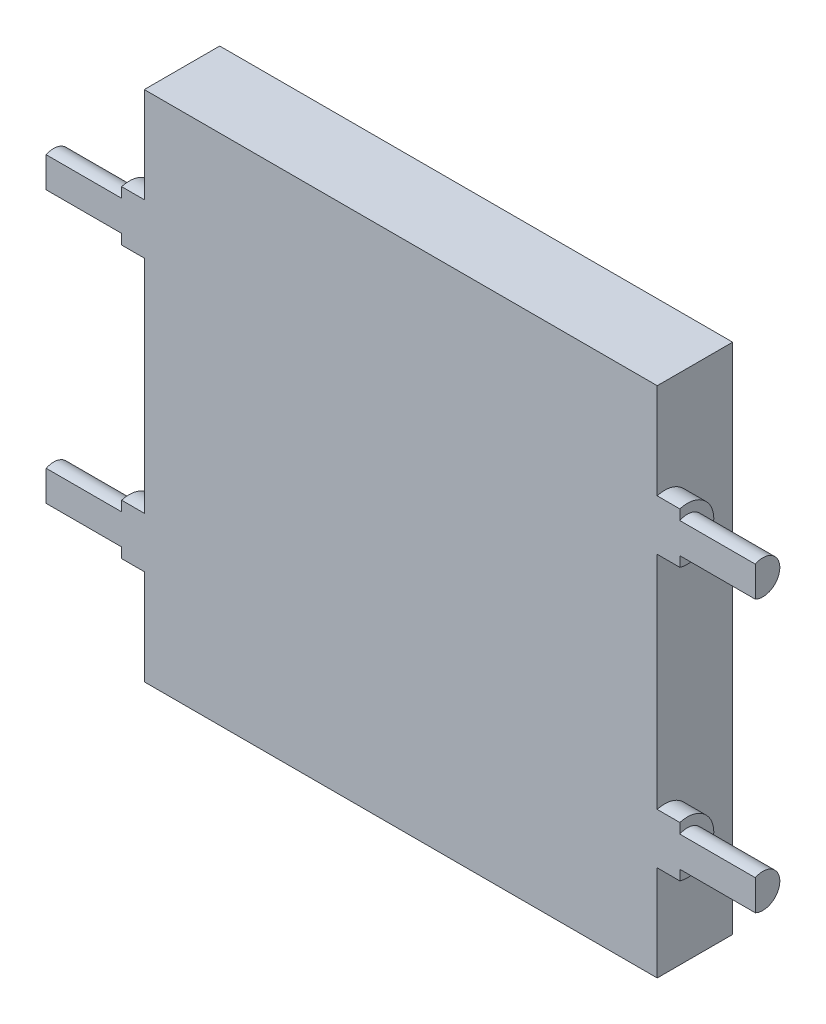
SolidWorks part; units mm, degrees
ref_plane "Front Plane" through (0, 0, 0) normal (0, 0, 1) x (1, 0, 0)
ref_plane "Top Plane" through (0, 0, 0) normal (0, 1, 0) x (1, 0, 0)
ref_plane "Right Plane" through (0, 0, 0) normal (1, 0, 0) x (0, 0, -1)
sketch "Sketch1" plane through (0, 0, 0) normal (0, 0, 1) x (1, 0, 0)
  line L1 (0, 0) -> (-68, 0)
  line L2 (0, 0) -> (0, -68)
  line L3 (0, -68) -> (-68, -68)
  line L4 (-68, 0) -> (-68, -68)
  dimension "D1" = 68
  dimension "D2" = 68
extrude "Boss-Extrude1" add sketch "Sketch1" along normal blind 10
sketch "Sketch2" plane through (-68, 0, 0) normal (-1, 0, 0) x (0, 0, 1)
  line L1 (10, 0) -> (0, 0) construction
  line L2 (10, -68) -> (0, -68) construction
  line L3 (10, 0) -> (10, -68) construction
  line L4 (10, 0) -> (10, -68)
  circle A0 centre (9, -52) radius 3.5
  circle A1 centre (9, -16) radius 3.5
  point P15 (0, 0)
  dimension "D1" = 7
  dimension "D2" = 7
  dimension "D3" = 1
  dimension "D4" = 0
  dimension "D5" = 16
  dimension "D6" = 16
extrude "Boss-Extrude2" add sketch "Sketch2" along normal blind 3 contours L4 A1 | L4 A0 region at (-68, -52, 8.0379) region at (-68, -16, 8.0379)
sketch "Sketch3" plane through (-71, 0, 0) normal (-1, 0, 0) x (0, 0, 1)
  line L0 (10, -55.3541) -> (10, -12.6459)
  circle A0 centre (9, -52) radius 2.25
  circle A1 centre (9, -16) radius 2.25
  dimension "D1" = 4.5
  dimension "D2" = 4.5
extrude "Boss-Extrude3" add sketch "Sketch3" along normal blind 10 contours L0 A0 | L0 A1 region at (-71, -52, 8.5562) region at (-71, -16, 8.5562)
sketch "Sketch4" plane through (0, 0, 0) normal (1, 0, 0) x (0, 0, -1)
  line L0 (-10, 0) -> (0, 0) construction
  line L1 (-10, -68) -> (0, -68) construction
  line L2 (-10, 0) -> (-10, -68)
  circle A0 centre (-9, -16) radius 3.5
  circle A1 centre (-9, -52) radius 3.5
  dimension "D1" = 16
  dimension "D2" = 16
  dimension "D3" = 7
  dimension "D4" = 7
  dimension "D5" = 1
  dimension "D6" = 0
extrude "Boss-Extrude4" add sketch "Sketch4" along normal blind 3 contours L2 A0 | L2 A1 region at (0, -16, 8.0379) region at (0, -52, 8.0379)
sketch "Sketch5" plane through (3, 0, 0) normal (1, 0, 0) x (0, 0, -1)
  line L0 (-10, -12.6459) -> (-10, -55.3541)
  circle A0 centre (-9, -16) radius 2.25
  circle A1 centre (-9, -52) radius 2.25
  dimension "D1" = 4.5
  dimension "D2" = 4.5
extrude "Boss-Extrude5" add sketch "Sketch5" along normal blind 10 contours L0 A0 | L0 A1 region at (3, -16, 8.5562) region at (3, -52, 8.5562)
sketch "Sketch6" plane through (0, 0, 0) normal (0, 0, -1) x (-1, 0, 0)
  line L0 (0, -34) -> (68, -34) construction
  line L1 (55.25, -12.75) -> (12.75, -12.75)
  line L2 (55.25, -12.75) -> (55.25, -55.25)
  line L3 (55.25, -55.25) -> (12.75, -55.25)
  line L4 (12.75, -12.75) -> (12.75, -55.25)
  line L5 (0, -68) -> (0, 0) construction
  line L6 (68, 0) -> (68, -68) construction
  line L7 (34, 0) -> (34, -68) construction
  line L8 (0, 0) -> (68, 0) construction
  line L9 (68, -68) -> (0, -68) construction
  point P16 (12.75, -34)
  point P17 (34, -55.25)
  dimension "D1" = 42.5
  dimension "D2" = 42.5
  dimension "D3" = 0
  dimension "D4" = 0
extrude "Cut-Extrude1" cut sketch "Sketch6" against normal blind 3
sketch "Sketch8" plane through (0, 0, 0) normal (0, 0, -1) x (-1, 0, 0)
  line L0 (55.25, -12.75) -> (12.75, -12.75) construction
  line L1 (12.75, -55.25) -> (55.25, -55.25) construction
  line L2 (12.75, -12.75) -> (12.75, -55.25) construction
  line L3 (34, 0) -> (34, -108.8236) construction
  line L4 (0, 0) -> (68, 0) construction
  circle A0 centre (4.75, -17.75) radius 1.5
  circle A1 centre (4.75, -50.25) radius 1.5
  circle A2 centre (63.25, -50.25) radius 1.5
  circle A3 centre (63.25, -17.75) radius 1.5
  dimension "D1" = 5
  dimension "D2" = 5
  dimension "D3" = 3
  dimension "D4" = 3
  dimension "D5" = 8
  dimension "D6" = 8
extrude "Cut-Extrude2" cut sketch "Sketch8" against normal blind 5
